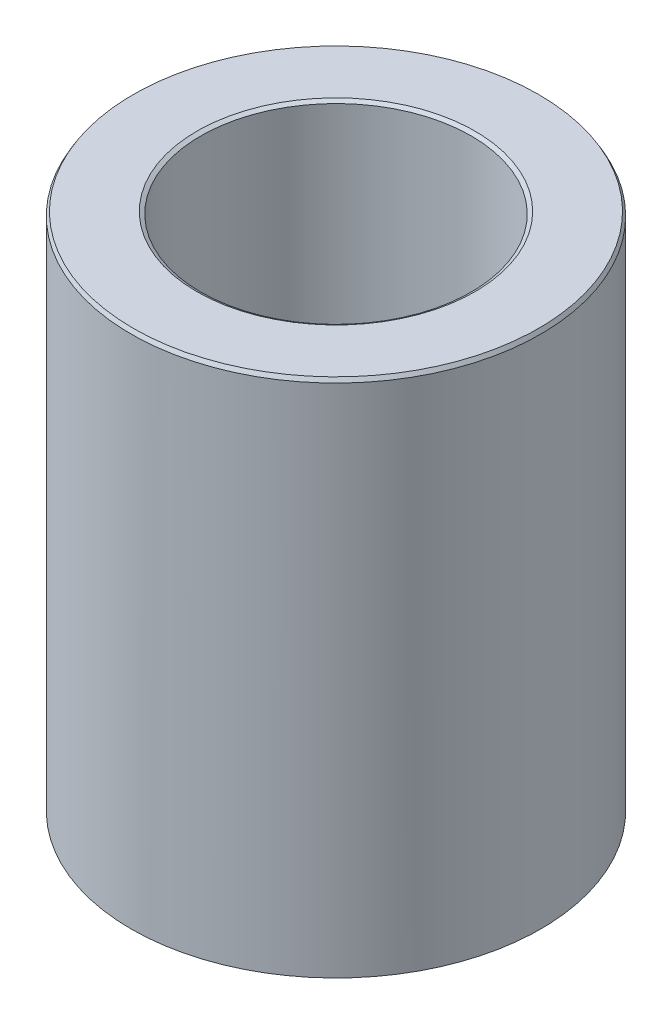
SolidWorks part; units mm, degrees
ref_plane "Front Plane" through (0, 0, 0) normal (0, 0, 1) x (1, 0, 0)
ref_plane "Top Plane" through (0, 0, 0) normal (0, 1, 0) x (1, 0, 0)
ref_plane "Right Plane" through (0, 0, 0) normal (1, 0, 0) x (0, 0, -1)
sketch "Sketch1" plane through (0, 0, 0) normal (0, 1, 0) x (1, 0, 0)
  circle A0 centre (0, 0) radius 40
  dimension "SLEEVE_OD" = 80
extrude "Boss-Extrude1" add sketch "Sketch1" along normal blind 101.7892
sketch "Sketch2" plane through (0, 0, 0) normal (0, 1, 0) x (1, 0, 0)
  circle A0 centre (0, 0) radius 26.4119
  dimension "BORE_D" = 52.8238
extrude "Cut-Extrude1" cut sketch "Sketch2" along normal through all
chamfer "Chamfer1" distance 0.7487 angle 30 4 edges at (0, 101.7892, 26.4119) (0, 0, 26.4119) (0, 0, 40) (0, 101.7892, 40) first distance on face at (0, 101.7892, 26.4119) first distance on face at (0, 0, 26.4119) first distance on face at (0, 101.7892, 40)
